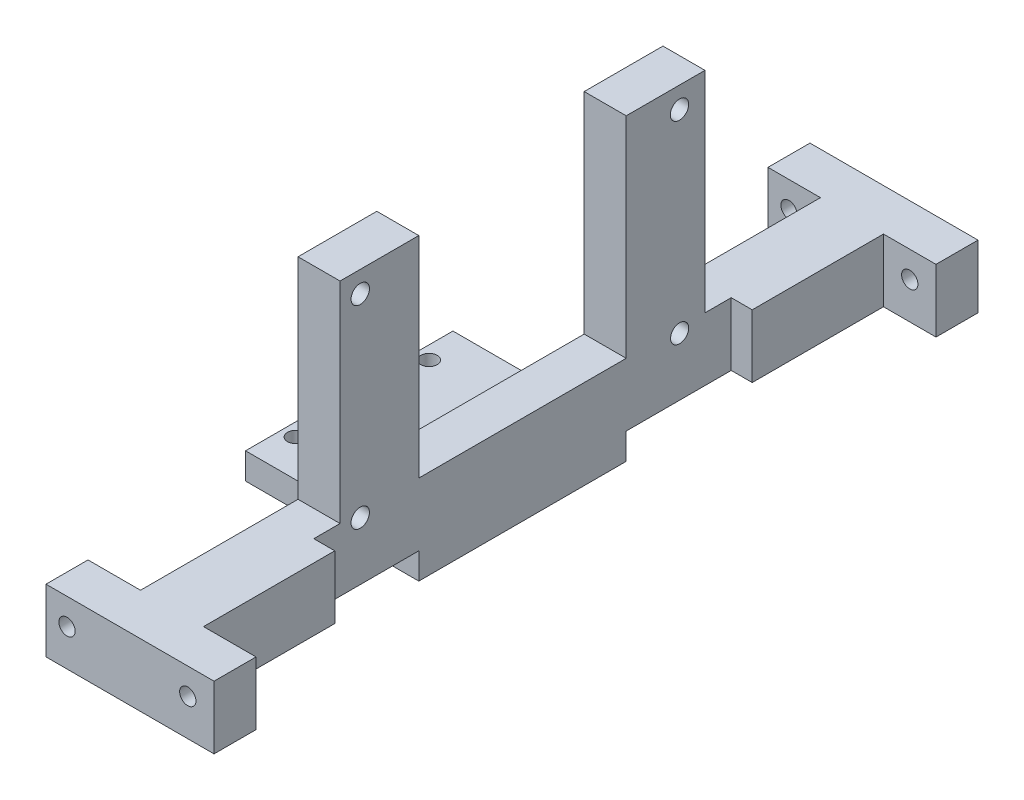
SolidWorks part; units mm, degrees
ref_plane "前视基准面" through (0, 0, 0) normal (0, 0, 1) x (1, 0, 0)
ref_plane "上视基准面" through (0, 0, 0) normal (0, 1, 0) x (1, 0, 0)
ref_plane "右视基准面" through (0, 0, 0) normal (1, 0, 0) x (0, 0, -1)
other "Configuration Table"
sketch "草图1" plane through (0, 0, 0) normal (0, 0, 1) x (1, 0, 0)
  line L5 (-6, 6) -> (6, 6)
  line L6 (-6, 6) -> (-6, -6)
  line L7 (-6, -6) -> (6, -6)
  line L8 (6, 6) -> (6, -6)
  line L9 (0, -6) -> (0, 6) construction
  line L10 (-6, 0) -> (6, 0) construction
  point P0 (0, 0)
  dimension "D1" = 12
  dimension "D2" = 12
extrude "凸台-拉伸1" add sketch "草图1" along normal blind 129.5
sketch "草图3" plane through (0, 0, 129.5) normal (0, 0, 1) x (1, 0, 0)
  line L1 (-16, 6) -> (16, 6)
  line L2 (-16, 6) -> (-16, -6)
  line L3 (-16, -6) -> (16, -6)
  line L4 (16, 6) -> (16, -6)
  line L5 (0, -6) -> (0, 6) construction
  line L6 (-16, 0) -> (16, 0) construction
  point P0 (0, 0)
  dimension "D1" = 12
  dimension "D2" = 32
extrude "凸台-拉伸2" add sketch "草图3" along normal blind 8
sketch "草图4" plane through (0, 0, 0) normal (0, 0, -1) x (-1, 0, 0)
  line L4 (16, 6) -> (-16, 6)
  line L5 (16, -6) -> (16, 6)
  line L6 (-16, -6) -> (16, -6)
  line L7 (-16, 6) -> (-16, -6)
  line L8 (16, 6) -> (-16, 6)
  line L9 (16, -6) -> (16, 6)
  line L10 (-16, -6) -> (16, -6)
  line L11 (-16, 6) -> (-16, -6)
  dimension "D1" = 0
extrude "凸台-拉伸3" add sketch "草图4" along normal blind 8
sketch "草图5" plane through (-6, 0, 0) normal (-1, 0, 0) x (0, 0, 1)
  line L0 (129.5, -6) -> (0, -6) construction
  line L1 (25, -6) -> (104.5, -6)
  line L2 (25, -6) -> (25, 46)
  line L3 (25, 46) -> (104.5, 46)
  line L4 (104.5, -6) -> (104.5, 46)
  line L7 (129.5, 6) -> (0, 6) construction
  dimension "D1" = 79.5
  dimension "D3" = 40
extrude "凸台-拉伸4" add sketch "草图5" against normal blind 8
sketch "草图6" plane through (2, 0, 0) normal (1, 0, 0) x (0, 0, -1)
  line L0 (-104.5, 46) -> (-25, 46) construction
  line L1 (-94.5, 46) -> (-35, 46)
  line L2 (-94.5, 46) -> (-94.5, 6)
  line L3 (-94.5, 6) -> (-35, 6)
  line L4 (-35, 46) -> (-35, 6)
  line L5 (-129.5, 6) -> (0, 6) construction
  line L6 (-104.5, 6) -> (-104.5, 46) construction
  line L7 (-25, 46) -> (-25, 6) construction
  dimension "D1" = 10
  dimension "D2" = 10
extrude "切除-拉伸1" cut sketch "草图6" against normal blind 10
sketch "草图10" plane through (0, 0, 35) normal (0, 0, 1) x (1, 0, 0)
  line L5 (-6, 6) -> (2, 6)
  line L7 (2, 6) -> (2, 46)
  line L8 (2, 46) -> (-6, 46)
  line L9 (-6, 46) -> (-6, 6)
  line L10 (-6, 6) -> (2, 6)
  line L12 (2, 6) -> (2, 46)
  line L13 (2, 46) -> (-6, 46)
  line L14 (-6, 46) -> (-6, 6)
  dimension "D1" = 0
extrude "凸台-拉伸7" add sketch "草图10" along normal blind 10
sketch "草图11" plane through (0, 0, 94.5) normal (0, 0, -1) x (-1, 0, 0)
  line L5 (6, 46) -> (-2, 46)
  line L6 (-2, 46) -> (-2, 6)
  line L8 (-2, 6) -> (6, 6)
  line L9 (6, 6) -> (6, 46)
  line L10 (6, 46) -> (-2, 46)
  line L11 (-2, 46) -> (-2, 6)
  line L13 (-2, 6) -> (6, 6)
  line L14 (6, 6) -> (6, 46)
  dimension "D1" = 0
extrude "凸台-拉伸8" add sketch "草图11" along normal blind 10
sketch "草图13" plane through (0, 0, 25) normal (0, 0, -1) x (-1, 0, 0)
  line L5 (-2, 6) -> (6, 6)
  line L6 (6, 6) -> (6, 46)
  line L7 (6, 46) -> (-2, 46)
  line L8 (-2, 46) -> (-2, 6)
  line L10 (-2, 6) -> (6, 6)
  line L11 (6, 6) -> (6, 46)
  line L12 (6, 46) -> (-2, 46)
  line L13 (-2, 46) -> (-2, 6)
  dimension "D1" = 0
extrude "切除-拉伸3" cut sketch "草图13" against normal blind 5
sketch "草图14" plane through (0, 0, 104.5) normal (0, 0, 1) x (1, 0, 0)
  line L5 (-6, 6) -> (2, 6)
  line L7 (2, 6) -> (2, 46)
  line L8 (2, 46) -> (-6, 46)
  line L9 (-6, 46) -> (-6, 6)
  line L10 (-6, 6) -> (2, 6)
  line L12 (2, 6) -> (2, 46)
  line L13 (2, 46) -> (-6, 46)
  line L14 (-6, 46) -> (-6, 6)
  dimension "D1" = 0
extrude "切除-拉伸4" cut sketch "草图14" against normal blind 5
sketch "草图17" plane through (0, 0, 129.5) normal (0, 0, -1) x (-1, 0, 0)
  circle A1 centre (12, 1) radius 1.55
  circle A2 centre (12, 1) radius 1.55
  circle A3 centre (-11, 1) radius 1.55
  circle A4 centre (-11, 1) radius 1.55
  dimension "D1" = 0
  dimension "D2" = 0
extrude "切除-拉伸5" cut sketch "草图17" against normal through all
extrude "切除-拉伸6" cut sketch "草图17<2>" along normal through all
sketch "草图17<2>" plane through (0, 0, 129.5) normal (0, 0, -1) x (-1, 0, 0) same geometry as "草图17"
sketch "草图19" plane through (0, 6, 0) normal (0, 1, 0) x (1, 0, 0)
  line L6 (6, -129.5) -> (6, 0) construction
  line L7 (6, -25) -> (2, -25)
  line L8 (6, -25) -> (6, -104.5)
  line L9 (6, -104.5) -> (2, -104.5)
  line L10 (2, -25) -> (2, -104.5)
  line L11 (2, -30) -> (-6, -30) construction
  line L12 (-6, -99.5) -> (2, -99.5) construction
  line L13 (2, -84.5) -> (2, -99.5) construction
  dimension "D1" = 5
  dimension "D2" = 5
extrude "切除-拉伸7" cut sketch "草图19" against normal through all
sketch "草图20" plane through (0, -6, 0) normal (0, -1, 0) x (1, 0, 0)
  line L9 (-6, 129.5) -> (-6, 0) construction
  line L10 (-6, 84.5) -> (2, 84.5)
  line L11 (-6, 84.5) -> (-6, 45)
  line L12 (-6, 45) -> (2, 45)
  line L13 (2, 84.5) -> (2, 45)
  line L14 (2, 25) -> (2, 104.5) construction
  line L15 (2, 104.5) -> (6, 104.5) construction
  line L16 (6, 25) -> (2, 25) construction
  dimension "D1" = 20
  dimension "D2" = 20
extrude "凸台-拉伸9" add sketch "草图20" along normal blind 5
sketch "草图21" plane through (-6, 0, 0) normal (-1, 0, 0) x (0, 0, 1)
  line L1 (45, -6) -> (84.5, -6)
  line L2 (45, -6) -> (45, -11)
  line L3 (45, -11) -> (84.5, -11)
  line L4 (84.5, -6) -> (84.5, -11)
extrude "凸台-拉伸10" add sketch "草图21" along normal blind 25
sketch "草图23" plane through (0, -11, 0) normal (0, -1, 0) x (1, 0, 0)
  line L0 (-31, 45) -> (-31, 84.5) construction
  line L1 (2, 84.5) -> (-31, 84.5) construction
  line L2 (-31, 45) -> (2, 45) construction
  circle A0 centre (-28.5, 77.45) radius 1.55
  circle A1 centre (-28.5, 52.05) radius 1.55
  dimension "D3" = 3.1
  dimension "D4" = 3.1
  dimension "D1" = 2.5
  dimension "D2" = 2.5
  dimension "D5" = 7.05
  dimension "D6" = 7.05
extrude "切除-拉伸8" cut sketch "草图23" against normal through all
sketch "草图25" plane through (2, 0, 0) normal (1, 0, 0) x (0, 0, -1)
  circle A0 centre (-95.65, 41.95) radius 1.75
  circle A1 centre (-95.65, 5.05) radius 1.75
  circle A2 centre (-34.826, 5.05) radius 1.726
  circle A3 centre (-34.85, 41.95) radius 1.75
extrude "切除-拉伸9" cut sketch "草图25" against normal up to next
sketch "草图26" plane through (0, 0, 45) normal (0, 0, -1) x (-1, 0, 0)
  line L0 (6, -6) -> (6, -1)
  line L1 (6, -1) -> (11, -6)
  line L2 (31, -6) -> (6, -6) construction
  line L3 (11, -6) -> (6, -6)
  dimension "D1" = 5
  dimension "D2" = 5
extrude "凸台-拉伸11" add sketch "草图26" along direction (0, 0, -1) on the side against the normal up to surface (39.5 mm away) up to face at (-12.8, -8, 84.5)
